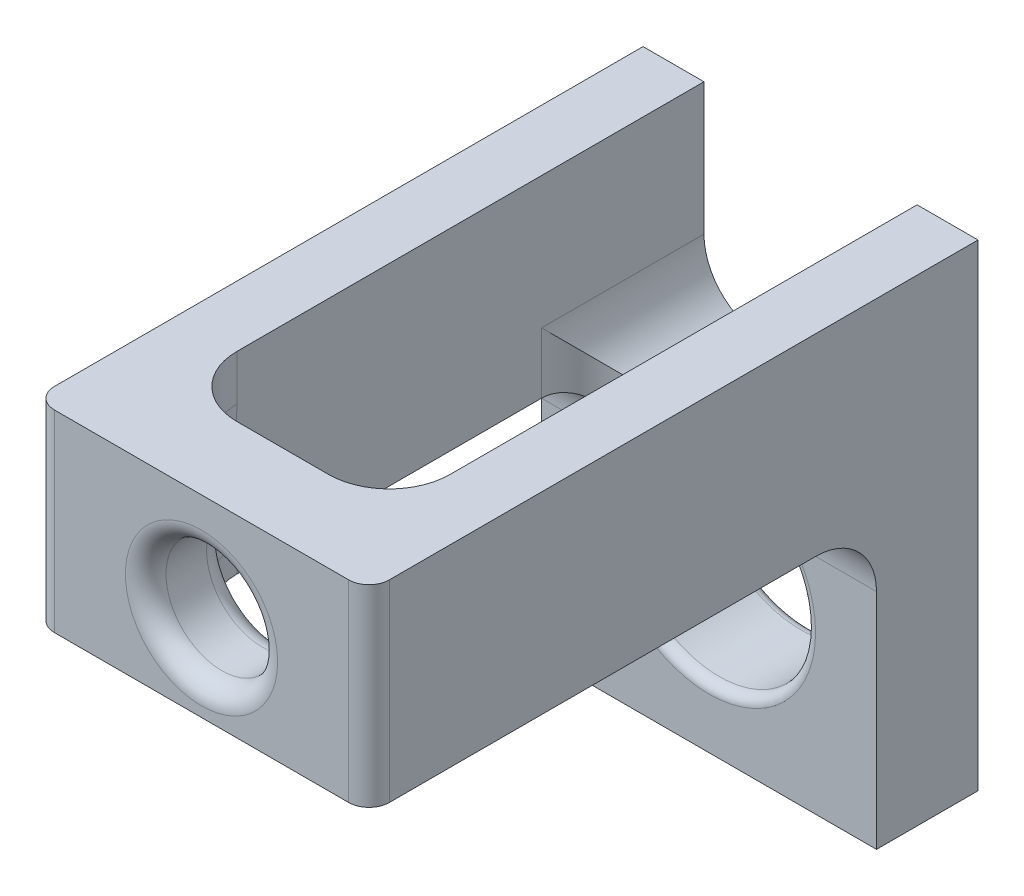
SolidWorks part; units mm, degrees
ref_plane "Front Plane" through (0, 0, 0) normal (0, 0, 1) x (1, 0, 0)
ref_plane "Top Plane" through (0, 0, 0) normal (0, 1, 0) x (1, 0, 0)
ref_plane "Right Plane" through (0, 0, 0) normal (1, 0, 0) x (0, 0, -1)
sketch "Sketch1" plane through (0, 0, 0) normal (0, 0, 1) x (1, 0, 0)
  line L0 (-8.25, 15.75) -> (-8.25, -7.75)
  line L1 (-8.25, -7.75) -> (8.25, -7.75)
  line L2 (8.25, -7.75) -> (8.25, 15.75)
  line L3 (8.25, 15.75) -> (-8.25, 15.75)
  line L4 (0, 15.75) -> (0, -7.75) construction
  line L5 (-8.25, 14.75) -> (-8.25, 6.25)
  line L6 (8.25, 14.75) -> (5.25, 14.75)
  line L7 (8.25, 14.75) -> (8.25, 6.25)
  line L8 (8.25, 6.25) -> (5.25, 6.25)
  line L9 (5.25, 14.75) -> (5.25, 6.25)
  line L10 (-8.25, 6.25) -> (-5.25, 6.25)
  line L11 (-8.25, 14.75) -> (-5.25, 14.75)
  line L12 (-5.25, 14.75) -> (-5.25, 6.25)
  line L13 (2.75, 10.5) -> (5.25, 10.5) construction
  line L14 (5.25, 6.25) -> (-5.25, 6.25)
  line L15 (5.25, 14.75) -> (-5.25, 14.75)
  line L16 (-5.25, 14.75) -> (-5.25, 15.75)
  line L17 (5.25, 14.75) -> (5.25, 15.75)
  circle A0 centre (0, 0) radius 4.75
  circle A1 centre (0, 10.5) radius 2.75
  circle A2 centre (0, 0) radius 6.375 construction
  point P5 (0, 13.25)
  point P13 (0, -4.75)
  point P14 (4.75, 0)
  dimension "D1" = 9.5
  dimension "D3" = 5.5
  dimension "D4" = 1
  dimension "D5" = 3.5
  dimension "D9" = 12.75
  dimension "D2" = 10.5
  dimension "D6" = 8.5
  dimension "D7" = 3
  dimension "D8" = 3
extrude "Boss-Extrude4" add sketch "Sketch1" against normal blind 5 contours L11 L12 L10 L0 L1 L2 L8 L9 L6 L3 A1 | A0 | L6 L9 L8 L2 | L12 L11 L0 L10 | L11 L16 L3 L0 | L17 L6 L2 L3 region at (-6.75, 15.25, 0) region at (-6.75, 10.5, 0) region at (-6.75, 6.0336, 0) region at (6.75, 15.25, 0) region at (6.75, 10.5, 0)
extrude "Boss-Extrude5" add sketch "Sketch1<8>" along normal blind 25 contours L3 L9 L8 L2 | L12 L3 L0 L10 | L17 L6 L2 L3 | L11 L16 L3 L0 region at (-6.75, 15.25, 0) region at (-6.75, 10.5, 0) region at (6.75, 15.25, 0) region at (6.75, 10.5, 0)
sketch "Sketch1<8>" plane through (0, 0, 0) normal (0, 0, 1) x (1, 0, 0) same geometry as "Sketch1"
extrude "Boss-Extrude7" add sketch "Sketch1<9>" against normal blind 4 from vertex contours L14 L9 L3 L12 A1 | L15 L17 L3 L16 region at (0, 15.25, 0) region at (0, 14.6149, 0) starting at point (8.25, 6.25, 25)
sketch "Sketch1<9>" plane through (0, 0, 0) normal (0, 0, 1) x (1, 0, 0) same geometry as "Sketch1"
fillet "Fillet1" radius 1 2 edges at (2.75, 10.5, 25) (2.75, 10.5, 21)
fillet "Fillet2" radius 3 4 edges at (-5.25, 11, 21) (5.25, 11, 21) (5.25, 6.25, -2.5) (-5.25, 6.25, -2.5)
fillet "Fillet3" radius 3 4 edges at (5.25, 7.75, 0) (-5.25, 7.75, 0) (-6.75, 6.25, 0)
fillet "Fillet4" radius 1 2 edges at (-8.25, 11, 25) (8.25, 11, 25)
fillet "Fillet5" radius 0.5 7 edges at (0, 4.75, 0) (0, -4.75, 0) (4.75, 0, -5)
